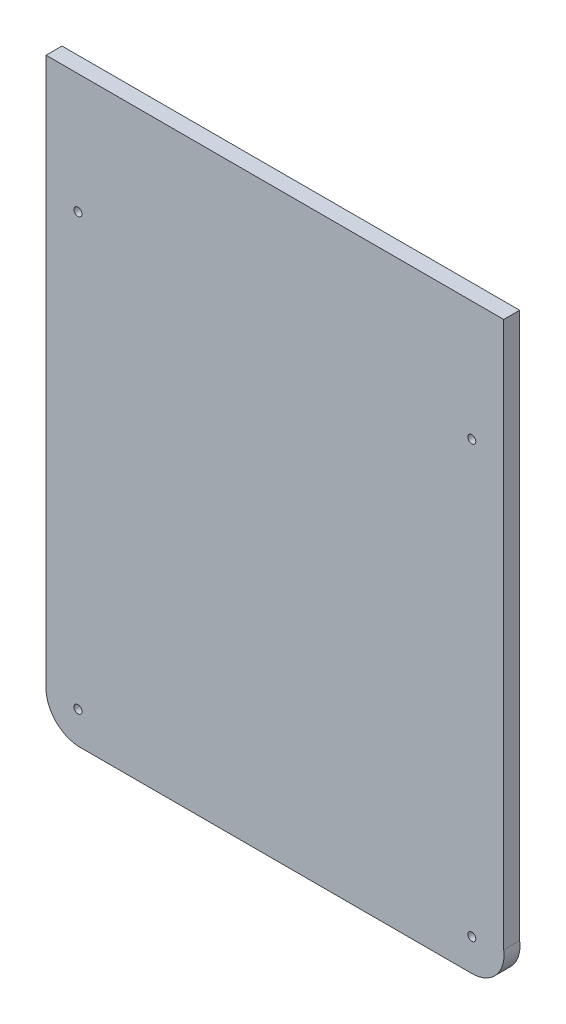
SolidWorks part; units mm, degrees
material "Beech"
ref_plane "Front Plane" through (0, 0, 0) normal (0, 0, 1) x (1, 0, 0)
ref_plane "Top Plane" through (0, 0, 0) normal (0, 1, 0) x (1, 0, 0)
ref_plane "Right Plane" through (0, 0, 0) normal (1, 0, 0) x (0, 0, -1)
sketch "Sketch1" plane through (0, 0, 0) normal (0, 0, 1) x (1, 0, 0)
  line L0 (-19.05, 903.0272) -> (-19.05, 155.124) construction
  line L1 (163.1, 903.0272) -> (163.1, 155.124) construction
  line L2 (-19.05, 920.1747) -> (163.1, 920.1747)
  line L5 (163.1, 683.9522) -> (163.1, 855.4022) construction
  line L6 (-6.35, 688.3997) -> (150.4, 688.3997)
  line L7 (163.1, 702.8437) -> (163.1, 920.1747)
  line L10 (-19.05, 920.1747) -> (-19.05, 701.0997)
  arc A2 (-19.05, 701.0997) -> (-6.35, 688.3997) centre (-5.3248, 702.1249) ccw
  arc A3 (150.4, 688.3997) -> (163.1, 702.8437) centre (150.5204, 701.0991) ccw
extrude "Boss-Extrude1" add sketch "Sketch1" along normal blind 6.35
hole_wizard "Hole1" positions "Sketch2" profile "Sketch3" legacy
sketch "Sketch2" plane through (72.025, -420.4895, 19.05) normal (0, 0, 1) x (1, 0, 0)
  point P0 (-78.375, 1293.0392)
  point P3 (-78.375, 1121.5892)
  point P6 (78.375, 1121.5892)
  point P9 (78.375, 1293.0392)
  point P12 (-764.0155, 1530.0782)
sketch "Sketch3" plane through (-6.35, 872.5497, 19.05) normal (1, 0, 0) x (0, -1, 0)
  line L0 (0, 0) -> (0, 32.7039)
  line L1 (0, 32.7039) -> (1.5875, 31.75)
  line L2 (1.5875, 31.75) -> (1.5875, 4.0177)
  line L3 (1.5875, 4.0177) -> (5.08, 0)
  line L4 (5.08, 0) -> (0, 0)
  line L5 (0, -14.3089) -> (0, 102.4216) construction
  line L6 (0, 32.7039) -> (-1.5875, 31.75) construction
  line L7 (-1.5875, 4.0177) -> (-5.08, 0) construction
  dimension "Diameter" = 3.175
  dimension "Depth" = 31.75
  dimension "C-Sink Diameter" = 10.16
  dimension "C-Sink Angle" = 82
  dimension "Drill Angle" = 118
